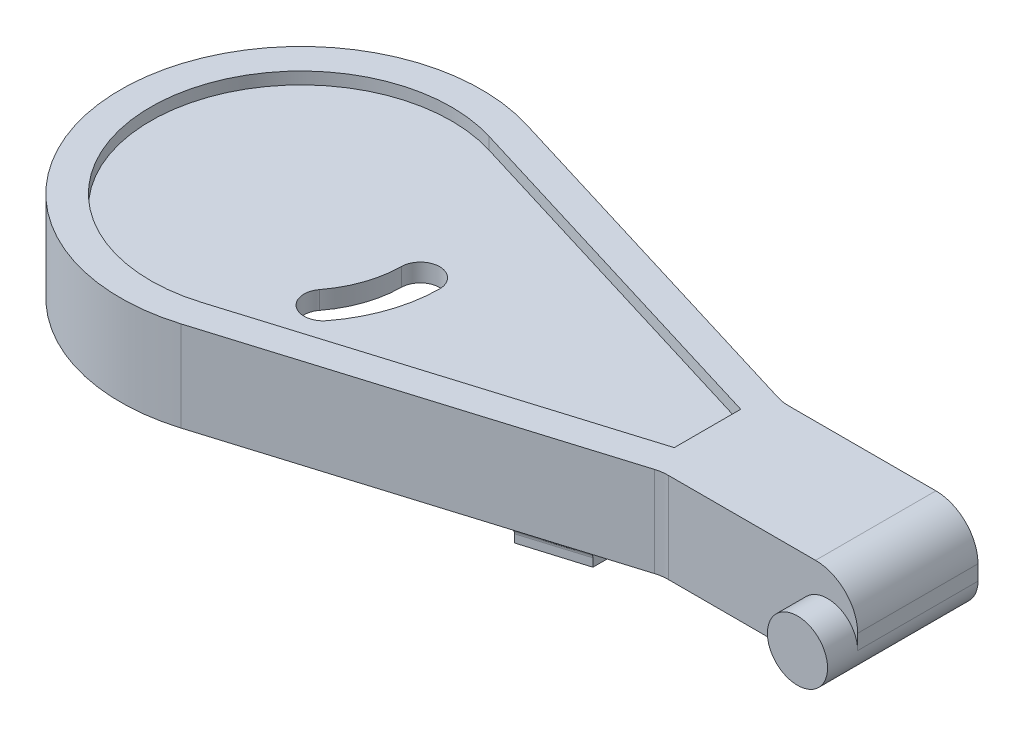
SolidWorks part; units mm, degrees
material "ABS"
ref_plane "前基準面" through (0, 0, 0) normal (0, 0, 1) x (1, 0, 0)
ref_plane "上基準面" through (0, 0, 0) normal (0, 1, 0) x (1, 0, 0)
ref_plane "右基準面" through (0, 0, 0) normal (1, 0, 0) x (0, 0, -1)
sketch "草圖1" plane through (0, 0, 0) normal (0, 1, 0) x (1, 0, 0)
  line L1 (-17.5, -10) -> (17.5, -10)
  line L2 (-17.5, -10) -> (-17.5, 10)
  line L3 (-17.5, 10) -> (17.5, 10)
  line L4 (17.5, -10) -> (17.5, 10)
  line L5 (-17.5, -10) -> (17.5, 10) construction
  line L6 (-17.5, 10) -> (17.5, -10) construction
  point P0 (0, 0)
  dimension "D1" = 35
  dimension "D2" = 20
extrude "填料-伸長1" add sketch "草圖1" along normal blind 10 and the other way blind 5
sketch "草圖6" plane through (0, 10, 0) normal (0, 1, 0) x (1, 0, 0)
  line L0 (-17.5, 10) -> (-17.5, -10) construction
  line L1 (-17.5, 5.5) -> (5.5, 5.5)
  line L2 (-17.5, 5.5) -> (-17.5, -5.5)
  line L3 (-17.5, -5.5) -> (5.5, -5.5)
  line L4 (5.5, 5.5) -> (5.5, -5.5)
  line L5 (-1000, 0) -> (49000, 0) construction
  line L6 (17.5, -10) -> (17.5, 10) construction
  dimension "D1" = 11
  dimension "D2" = 12
extrude "除料-伸長2" cut sketch "草圖6" against normal blind 10
sketch "草圖17" plane through (0, 0, 10) normal (0, 0, 1) x (1, 0, 0)
  line L0 (17.5, -5) -> (17.5, 10) construction
  circle A1 centre (10, 4.5) radius 5
  dimension "D1" = 10
  dimension "D2" = 7.5
extrude "填料-伸長3" add sketch "草圖17" along normal blind 5
sketch "草圖7" plane through (0, 0, -10) normal (0, 0, 1) x (1, 0, 0)
  line L1 (17.5, 10) -> (17.5, -5) construction
  line L6 (13, 4.5) -> (49022, 4.5) construction
  circle A0 centre (10, 4.5) radius 3
  dimension "D1" = 6
  dimension "D2" = 7.5
extrude "除料-伸長7" cut sketch "草圖7" against normal mid plane 10
sketch "草圖12" plane through (0, 0, 0) normal (0, 0, 1) x (1, 0, 0)
  line L0 (15, 4.5) -> (15, -5)
  line L1 (15, -5) -> (17.5465, -5)
  line L2 (7.5817, 8.8763) -> (5.5465, 8.8763)
  line L4 (5.5465, 8.8763) -> (5.5465, 10.4978)
  line L5 (5.5465, 10.4978) -> (17.5465, 10.4978)
  line L6 (17.5465, 10.4978) -> (17.5465, -5)
  arc A0 (15, 4.5) -> (7.5817, 8.8763) centre (10, 4.5) ccw
  dimension "D1" = 10
  dimension "D2" = 12
extrude "除料-伸長12" cut sketch "草圖12" against normal through all both and the other way through all
sketch "草圖14" plane through (0, -5, 0) normal (0, 1, 0) x (1, 0, 0)
  line L0 (-17.5, 10) -> (-78.7419, 28.6931)
  line L1 (-78.7419, -28.6931) -> (-17.5, -10)
  line L2 (-17.5, 10) -> (-17.5, -10)
  arc A0 (-78.7419, 28.6931) -> (-78.7419, -28.6931) centre (-87.5, 0) ccw
  dimension "D1" = 30
  dimension "D2" = 70
extrude "填料-伸長2" add sketch "草圖14" along normal blind 15
sketch "草圖15" plane through (0, 10, 0) normal (0, 1, 0) x (1, 0, 0)
  line L0 (-17.5, 5.5) -> (-80.1287, 24.4114)
  line L1 (-80.1287, -24.4114) -> (-17.5, -5.5)
  arc A0 (-80.1287, 24.4114) -> (-80.1287, -24.4114) centre (-87.5, 0) ccw
  line M3 (-17.5, -5.5) -> (-17.5, 5.5)
  dimension "D1" = 25.5
extrude "除料-伸長13" cut sketch "草圖15" against normal blind 10 and the other way through all contours L0 A0 L1 M3 region at (-72.0624, 10, 0)
sketch "草圖16" plane through (0, 0, 0) normal (0, 1, 0) x (1, 0, 0)
  line L0 (-87.5, 0) -> (-67.5008, -0.1745) construction
  line L1 (-87.5, 0) -> (-71.6329, -12.1752) construction
  line L2 (-1000, 0) -> (49000, 0) construction
  circle A2 centre (-87.5, 0) radius 20 construction
  arc A5 (-70.7006, -0.1466) -> (-74.1717, -10.2272) centre (-87.5, 0) cw
  arc A6 (-64.3009, -0.2025) -> (-69.0942, -14.1233) centre (-87.5, 0) cw
  arc A8 (-70.7006, -0.1466) -> (-64.3009, -0.2025) centre (-67.5008, -0.1745) cw
  arc A9 (-74.1717, -10.2272) -> (-69.0942, -14.1233) centre (-71.6329, -12.1752) ccw
  dimension "D1" = 3.2
  dimension "D2" = 3.2
  dimension "D3" = 40
  dimension "D4" = 37
  dimension "D5" = 3.2
  dimension "D6" = 0.5
extrude "除料-伸長14" cut sketch "草圖16" against normal blind 3 contours A5 region at (-69.0987, 0, 6.3361)
fillet "圓角1" radius 7 3 edges at (15, -5, 0) (-17.5, 2.5, -10) (-17.5, 2.5, 10)
fillet "圓角2" radius 5 2 edges at (-17.5, 5, 5.5) (-17.5, 5, -5.5)
sketch "草圖18" plane through (0, 0, 0) normal (0, 0, 1) x (1, 0, 0)
  line L0 (4.7081, 9.9978) -> (13.9664, 9.9978)
  line L1 (13.9664, 9.9978) -> (4.7081, 4.5325)
  line L3 (4.7081, 4.5325) -> (4.7081, 9.9978)
extrude "除料-伸長15" cut sketch "草圖18" against normal mid plane 11
ref_plane "平面2" through (0, -5, 0) normal (0, 1, 0) x (1, 0, 0)
mirror "鏡射6" about plane through (0, -5, 0) normal (0, 1, 0) of "除料-伸長15", "圓角2", "圓角1", "除料-伸長14", "除料-伸長13", "填料-伸長2", "除料-伸長12", "除料-伸長7", "填料-伸長3", "除料-伸長2", "填料-伸長1"
sketch "草圖19" plane through (0, 0, 0) normal (1, 0, 0) x (0, 0, -1)
  line L0 (33, -5) -> (-33, -5) construction
  line L1 (-30, 10) -> (32.0765, 10)
  line L2 (-30, 10) -> (-30, -5)
  line L3 (-30, -5) -> (32.0765, -5)
  line L4 (32.0765, 10) -> (32.0765, -5)
extrude "除料-伸長16" cut sketch "草圖19" against normal through all both and the other way through all
sketch "草圖20" plane through (0, -20, 0) normal (0, -1, 0) x (1, 0, 0)
  line L0 (0, 0) -> (-21.1679, 0) construction
  line L2 (-26.5, -12.5) -> (-36.5, -15.5196)
  line L3 (-26.5, -12.5) -> (-26.5, 12.5)
  line L4 (-26.5, 12.5) -> (-36.5, 15.5196)
  line L5 (-36.5, -15.5196) -> (-36.5, 15.5196)
  line L7 (-80.1287, 24.4114) -> (-18.2069, 5.7135) construction
  line L8 (-114.5, -5) -> (-111.5, -5)
  line L9 (-114.5, -5) -> (-114.5, 5)
  line L10 (-114.5, 5) -> (-111.5, 5)
  line L11 (-111.5, -5) -> (-111.5, 5)
  arc A0 (-78.7419, 28.6931) -> (-78.7419, -28.6931) centre (-87.5, 0) ccw construction
  dimension "D1" = 10
  dimension "D2" = 3
  dimension "D3" = 24
  dimension "D4" = 26.5
  dimension "D5" = 10
  dimension "D6" = 25
extrude "填料-伸長4" add sketch "草圖20" along normal blind 2
fillet "圓角3" radius 1 5 edges at (-113.5025, -20, 5) (-113.5025, -20, -5) (-114.5, -20, 0) (-31.5, -20, 14.0098) (-31.5, -20, -14.0098)
sketch "草圖21" plane through (0, -5, 0) normal (0, 1, 0) x (1, 0, 0)
  line L6 (-80.2016, 23.9109) -> (-19.9587, 5.5228)
  line L7 (-80.2016, 23.9109) -> (-19.9587, 5.5228)
  line L8 (-19.9587, 5.5228) -> (-19.9587, -5.5228)
  line L9 (-80.2016, -23.9109) -> (-19.9587, -5.5228)
  line L10 (-80.2016, -23.9109) -> (-19.9587, -5.5228)
  arc A5 (-80.2016, 23.9109) -> (-80.2016, -23.9109) centre (-87.5, 0) ccw
  arc A6 (-80.2016, 23.9109) -> (-80.2016, -23.9109) centre (-87.5, 0) ccw
  dimension "D1" = 5
  dimension "D2" = 5
extrude "除料-伸長17" cut sketch "草圖21" against normal blind 2
